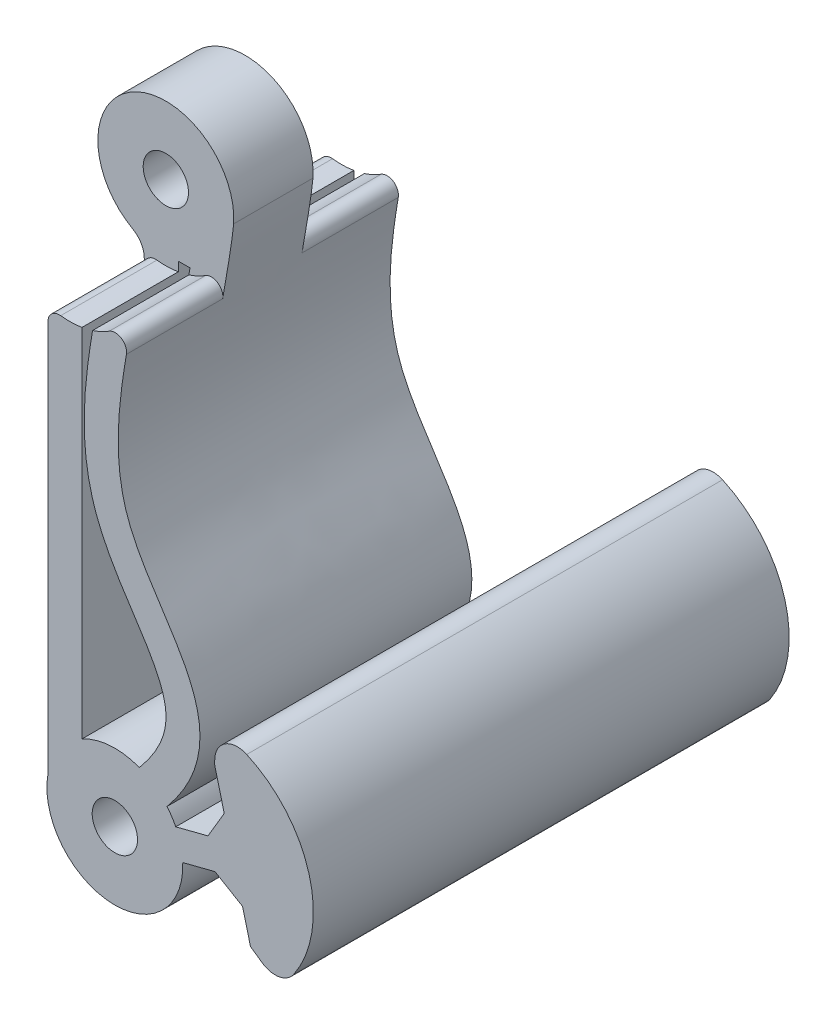
SolidWorks part; units mm, degrees
ref_plane "Front Plane" through (0, 0, 0) normal (0, 0, 1) x (1, 0, 0)
ref_plane "Top Plane" through (0, 0, 0) normal (0, 1, 0) x (1, 0, 0)
ref_plane "Right Plane" through (0, 0, 0) normal (1, 0, 0) x (0, 0, -1)
sketch "Sketch1" plane through (0, 0, 0) normal (0, 0, 1) x (1, 0, 0)
  line L3 (0.9027, 23.1193) -> (0.9027, 44.7293) construction
  line L4 (0.9027, 44.7293) -> (-1.0973, 44.7293) construction
  line L5 (-2.0488, 41.8842) -> (-2.0488, 23.6567)
  line L6 (-0.0313, 41.8842) -> (-0.5488, 41.8842)
  line L7 (-0.5488, 41.8842) -> (-0.5488, 25.7448)
  line L10 (-0.5488, 43.3332) -> (-0.5488, 23.4977) construction
  line L12 (1003.2054, 25.0421) -> (3.2054, 25.0421) construction
  line L13 (-2.0488, 41.8842) -> (49997.9512, 41.8842) construction
  line L14 (-0.5488, 25.0421) -> (-49996.7946, 25.0421) construction
  arc A0 (-2.0488, 41.8842) -> (1.896, 44.5297) centre (-1.0973, 44.7293) cw
  arc A2 (-2.0488, 23.6567) -> (3.2054, 25.0421) centre (0.9027, 23.1193) ccw
  circle A3 centre (-1.0973, 44.7293) radius 1
  circle A4 centre (0.9027, 23.1193) radius 1
  arc A7 (-0.5488, 23.4977) -> (0.9027, 24.6193) centre (0.9027, 23.1193) ccw construction
  arc A8 (-0.5488, 43.3332) -> (0.4006, 44.6513) centre (-1.0973, 44.7293) cw construction
  arc A9 (1.9829, 25.918) -> (-0.5488, 25.7448) centre (0.9027, 23.1193) ccw
  spline S0 degree 3 poles (1.896, 44.5297) (1.6161, 41.7589) (-0.9369, 33.9552) (6.8447, 29.4175) (3.2054, 25.0421) knots 0 0 0 0 0.461185 1 1 1 1
  spline S1 degree 1 poles (0.4006, 44.6513) (0.9027, 24.6193) knots 0 0 1 1 construction
  spline S2 degree 3 poles (0.4006, 44.6513) (0.3814, 44.4652) (0.3367, 44.1044) (0.2163, 43.3069) (0.0657, 42.4502) (-0.0914, 41.5355) (-0.2432, 40.5851) (-0.402, 39.3533) (-0.4791, 37.8282) (-0.3759, 36.2754) (0.01, 34.6811) (0.9413, 32.7707) (2.0354, 31.2469) (2.8047, 29.9095) (3.1286, 29.0309) (3.1964, 28.2674) (3.0323, 27.5503) (2.6663, 26.8291) (2.3349, 26.3502) (2.1068, 26.0672) (2.0129, 25.9541) (1.9549, 25.8844) (1.8019, 25.7008) (1.4593, 25.2881) (1.1253, 24.887) (0.9027, 24.6193) knots 0.001801 0.001801 0.001801 0.001801 0.034767 0.067734 0.132717 0.165683 0.1996 0.265533 0.331467 0.3974 0.463333 0.529266 0.661132 0.727066 0.792999 0.858932 0.924865 0.957832 0.990798 0.99904 1.001358 1.005479 1.00754 1.023765 1.056732 1.056732 1.056732 1.056732 only from (-0.0313, 41.8842) to (1.9829, 25.918)
  dimension "D1" = 2
  dimension "D2" = 3
  dimension "D3" = 21.61
  dimension "D4" = 2
  dimension "D5" = 1.5
  dimension "D6" = 6
  dimension "D7" = 1.5
extrude "Boss-Extrude1" add sketch "Sketch1" along normal blind 12
ref_plane "midplane" through (0, 0, 6) normal (0, 0, 1) x (1, 0, 0)
sketch "Sketch2" plane through (0, 0, 12) normal (0, 0, 1) x (1, 0, 0)
  circle A4 centre (-1.0973, 44.7293) radius 3.3
  dimension "D1" = 6.6
extrude "Cut-Extrude1" cut sketch "Sketch2" against normal blind 4.25
mirror "Mirror1" about plane through (0, 0, 6) normal (0, 0, 1) of "Cut-Extrude1"
sketch "Sketch3" plane through (0, 0, 6) normal (0, 0, 1) x (1, 0, 0)
  circle A2 centre (0.9027, 23.1193) radius 3.3
  dimension "D1" = 6.6
extrude "Cut-Extrude2" cut sketch "Sketch3" against normal blind 2.25 and the other way blind 2.25
ref_plane "Plane1" through (9.4512, 0, 0) normal (1, 0, 0) x (0, 0, -1)
sketch "Sketch6" plane through (0, 0, 0) normal (0, 0, 1) x (1, 0, 0)
  line L1 (4.6597, 28.4574) -> (-2.0488, 28.4574) construction
  line L2 (-2.0488, 41.5694) -> (-2.0488, 23.6567) construction
  line L4 (8.1477, 20.6439) -> (6.8888, 21.5287)
  line L5 (5.3117, 27.6705) -> (5.3117, 29.1888)
  arc A0 (5.3117, 29.1888) -> (8.1477, 20.6439) centre (4.6644, 24.2309) cw
  arc A1 (5.3117, 27.6705) -> (6.8888, 21.5287) centre (4.6644, 24.2309) cw
  dimension "D1" = 5
  dimension "D2" = 3.5
extrude "Boss-Extrude4" add sketch "Sketch6" along normal up to surface (12 mm away) and the other way blind 9 up to face at (0.5703, 30.8825, 12)
sketch "Sketch7" plane through (0, 0, 12) normal (0, 0, 1) x (1, 0, 0)
  line L3 (5.3117, 27.6705) -> (6.8888, 21.5287)
  arc A0 (6.8888, 21.5287) -> (5.3117, 27.6705) centre (4.6644, 24.2309) ccw construction
  arc A1 (6.8888, 21.5287) -> (5.3117, 27.6705) centre (4.6644, 24.2309) ccw
extrude "Boss-Extrude5" add sketch "Sketch7" against normal up to surface (21 mm away) up to face at (7.5736, 25.1058, -9)
sketch "Sketch8" plane through (0, 0, 12) normal (0, 0, 1) x (1, 0, 0)
  line L5 (0.9027, 23.1193) -> (6.1353, 24.463) construction
  line L6 (5.3117, 27.6705) -> (6.8888, 21.5287) construction
  line L7 (6.1353, 24.463) -> (5.9799, 25.0683)
  line L8 (5.9799, 25.0683) -> (3.2621, 24.3704)
  line L9 (3.2621, 24.3704) -> (3.573, 23.1597)
  line L10 (3.573, 23.1597) -> (6.2908, 23.8576)
  line L11 (6.2908, 23.8576) -> (6.1353, 24.463)
  line L12 (5.3117, 27.6705) -> (6.8888, 21.5287) construction
  line L13 (5.3117, 27.6705) -> (6.8888, 21.5287) construction
  dimension "D1" = 1.25
extrude "Boss-Extrude6" add sketch "Sketch8" against normal up to surface (3.75 mm away) up to face at (1.9027, 23.1193, 8.25)
sketch "Sketch10" plane through (0, 0, 0) normal (0, 0, -1) x (-1, 0, 0)
  line L8 (-3.2621, 24.3704) -> (-3.573, 23.1597) construction
  line L9 (-3.573, 23.1597) -> (-6.2908, 23.8576) construction
  line L10 (-6.2908, 23.8576) -> (-6.1353, 24.463) construction
  line L11 (-6.1353, 24.463) -> (-5.9799, 25.0683) construction
  line L12 (-5.9799, 25.0683) -> (-3.2621, 24.3704) construction
  line L13 (-3.2621, 24.3704) -> (-3.573, 23.1597)
  line L14 (-3.573, 23.1597) -> (-6.2908, 23.8576)
  line L15 (-6.2908, 23.8576) -> (-6.1353, 24.463)
  line L16 (-6.1353, 24.463) -> (-5.9799, 25.0683)
  line L17 (-5.9799, 25.0683) -> (-3.2621, 24.3704)
extrude "Boss-Extrude7" add sketch "Sketch10" against normal up to surface (3.75 mm away) up to face at (1.9027, 23.1193, 3.75)
fillet "Fillet1" radius 0.5 4 edges at (-2.0488, 41.5694, 2.125) (-2.0488, 41.5694, 9.875) (1.6708, 42.9328, 2.125) (1.6708, 42.9328, 9.875)
fillet "Fillet2" radius 1 1 edges at (-2.0488, 41.8842, 6)
fillet "Fillet10" radius 1 1 edges at (8.1477, 20.6439, 1.5)
fillet "Fillet11" radius 1 1 edges at (-2.0488, 24.5953, 6)
chamfer "Chamfer5" distance 1 angle 45 7 edges at (5.9799, 25.0683, 10.125) (6.1353, 24.463, 8.25) (6.2908, 23.8576, 10.125) (6.1353, 24.463, 3.75) (5.9799, 25.0683, 1.875) (6.2908, 23.8576, 1.875) (6.1353, 24.463, 0)
fillet "Fillet12" radius 1 1 edges at (5.3117, 29.1888, 1.5)
equation "\"axle-diameter\"=2"
equation "\"switch-thickness\"=12"
equation "\"base-width\"=4.0"
equation "\"axle-bushing-radius\"=3"
equation "\"D1@Sketch1\"=\"axle-diameter\""
equation "\"D2@Sketch1\"=\"axle-bushing-radius\""
equation "\"D1@Cut-Extrude1\"=\"switch-thickness\"/3+\"clearance\""
equation "\"D1@Cut-Extrude2\"=\"switch-thickness\"/6+\"clearance\""
equation "\"D2@Cut-Extrude2\"=\"switch-thickness\"/6+\"clearance\""
equation "\"D1@Boss-Extrude1\"=\"switch-thickness\""
equation "\"D1@Sketch2\"=\"axle-bushing-radius\"*2.2"
equation "\"D1@Sketch3\"=\"axle-bushing-radius\"*2.2"
equation "\"clearance\"= 0.25"
equation "\"arm-width\"=3.0"
equation "\"min-diameter\"=70"
